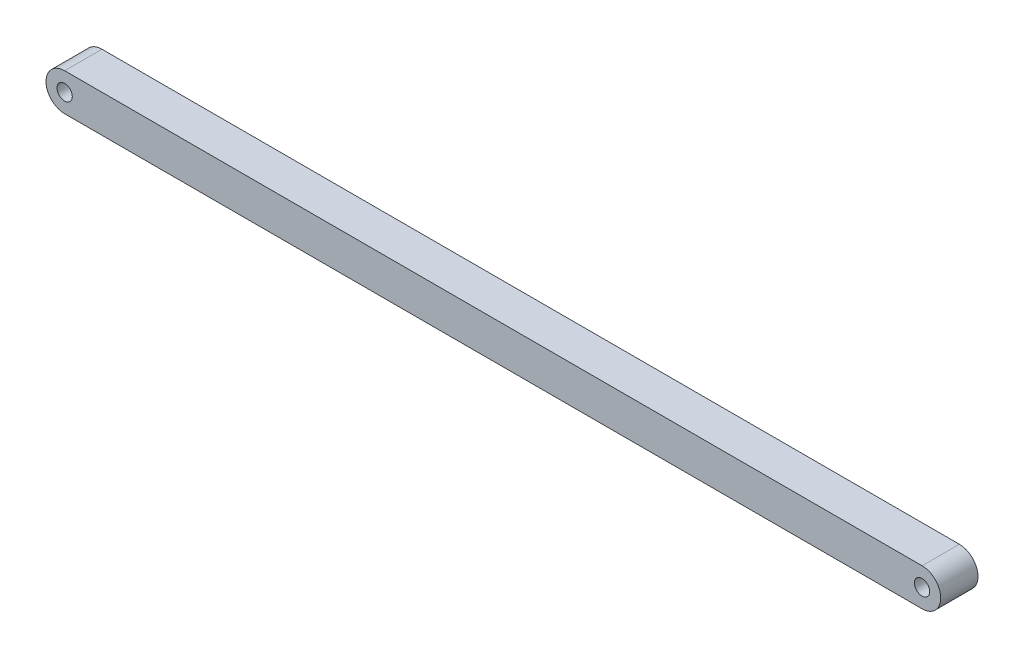
SolidWorks part; units mm, degrees
ref_plane "Ebene vorne" through (0, 0, 0) normal (0, 0, 1) x (1, 0, 0)
ref_plane "Ebene oben" through (0, 0, 0) normal (0, 1, 0) x (1, 0, 0)
ref_plane "Ebene rechts" through (0, 0, 0) normal (1, 0, 0) x (0, 0, -1)
sketch "Skizze1" plane through (0, 0, 0) normal (0, 0, 1) x (1, 0, 0)
  line L0 (-115, 0) -> (115, 0) construction
  line L1 (-115, 5) -> (115, 5)
  line L2 (-115, -5) -> (115, -5)
  arc A0 (-115, 5) -> (-115, -5) centre (-115, 0) ccw
  arc A1 (115, -5) -> (115, 5) centre (115, 0) ccw
  circle A2 centre (-115, 0) radius 2.05
  circle A3 centre (115, 0) radius 2.05
  point P2 (0, 0)
  dimension "D3" = 4.1
  dimension "D4" = 4.1
  dimension "D1" = 10
  dimension "D2" = 230
extrude "Aufsatz-Linear austragen1" add sketch "Skizze1" along normal blind 5 and the other way blind 5 contours L2 A1 L1 A0 A2 A3 region at (0, 0, 0)
